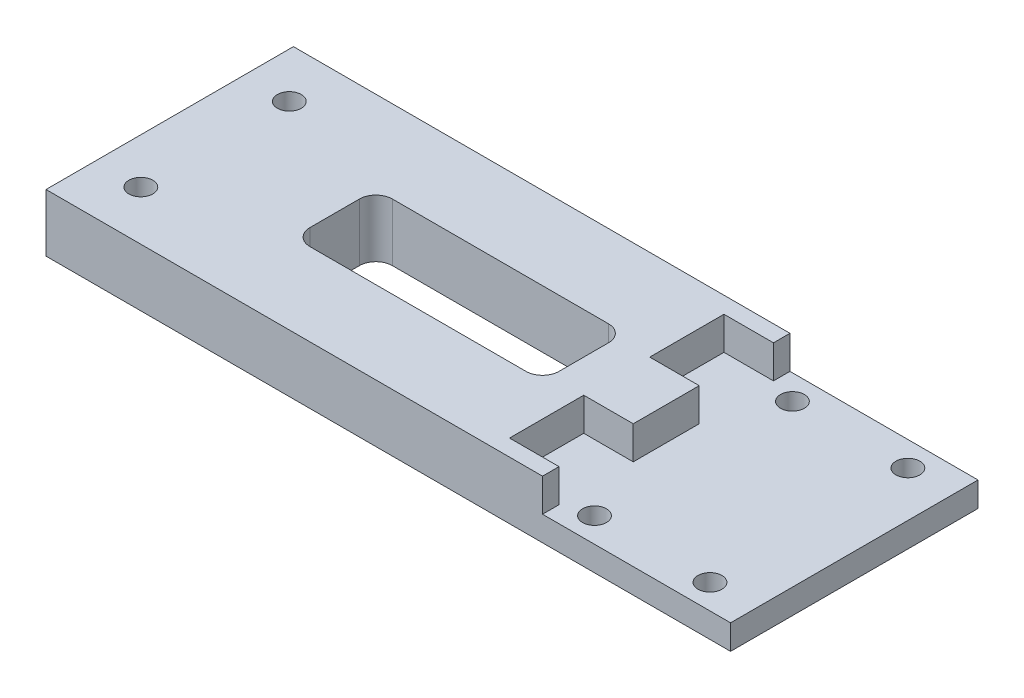
SolidWorks part; units mm, degrees
ref_plane "前视基准面" through (0, 0, 0) normal (0, 0, 1) x (1, 0, 0)
ref_plane "上视基准面" through (0, 0, 0) normal (0, 1, 0) x (1, 0, 0)
ref_plane "右视基准面" through (0, 0, 0) normal (1, 0, 0) x (0, 0, -1)
other "Configuration Table"
sketch "草图1" plane through (0, 0, 0) normal (0, 1, 0) x (1, 0, 0)
  line L1 (0, 0) -> (-88, 0)
  line L2 (0, 0) -> (0, 30)
  line L3 (0, 30) -> (-88, 30)
  line L4 (-88, 0) -> (-88, 30)
  dimension "D1" = 88
  dimension "D2" = 30
extrude "凸台-拉伸1" add sketch "草图1" along normal blind 3
sketch "草图2" plane through (0, 3, 0) normal (0, 1, 0) x (1, 0, 0)
  line L0 (-88, 0) -> (0, 0) construction
  line L1 (0, 30) -> (-27.8, 30)
  line L2 (0, 30) -> (0, 0)
  line L3 (0, 0) -> (-27.8, 0)
  line L4 (-27.8, 30) -> (-27.8, 0)
  dimension "D1" = 27.8
extrude "切除-拉伸1" cut sketch "草图2" against normal blind 1
sketch "草图3" plane through (0, 2, 0) normal (0, 1, 0) x (1, 0, 0)
  line L0 (-27.5, 30) -> (-27.5, 27) construction
  line L3 (-27.5, 27) -> (-24.5, 27) construction
  line L4 (-24.5, 27) -> (-24.5, 3) construction
  line L5 (-24.5, 3) -> (-10.5, 3) construction
  line L6 (-10.5, 3) -> (-10.5, 27) construction
  circle A4 centre (-24.5, 27) radius 1.45
  circle A5 centre (-24.5, 3) radius 1.45
  circle A6 centre (-10.5, 3) radius 1.45
  circle A7 centre (-10.5, 27) radius 1.45
  dimension "D6" = 2.9
  dimension "D1" = 3
  dimension "D2" = 3
  dimension "D3" = 24
  dimension "D4" = 14
  dimension "D5" = 24
extrude "切除-拉伸2" cut sketch "草图3" against normal blind 11
sketch "草图4" plane through (0, 3, 0) normal (0, 1, 0) x (1, 0, 0)
  line L0 (-88, 24) -> (-82.5, 24) construction
  line L2 (-27.8, 30) -> (-88, 30) construction
  line L3 (-88, 15) -> (-85.0043, 15) construction
  line L4 (-88, 30) -> (-88, 0) construction
  circle A0 centre (-82.5, 24) radius 1.45
  circle A1 centre (-82.5, 6) radius 1.45
  dimension "D2" = 2.9
  dimension "D1" = 5.5
  dimension "D3" = 6
extrude "切除-拉伸4" cut sketch "草图4" against normal blind 11
sketch "草图5" plane through (0, 3, 0) normal (0, 1, 0) x (1, 0, 0)
  line L0 (-88, 0) -> (-27.8, 0) construction
  line L1 (-68, 20) -> (-37.8, 20)
  line L2 (-68, 20) -> (-68, 10)
  line L3 (-68, 10) -> (-37.8, 10)
  line L4 (-37.8, 20) -> (-37.8, 10)
  line L5 (-27.8, 30) -> (-88, 30) construction
  line L6 (-27.8, 30) -> (-27.8, 0) construction
  line L7 (-88, 30) -> (-88, 0) construction
  dimension "D1" = 10
  dimension "D2" = 10
  dimension "D3" = 10
  dimension "D4" = 20
extrude "切除-拉伸5" cut sketch "草图5" against normal blind 11
fillet "圆角1" radius 2 4 edges at (-68, 1.5, -10) (-37.8, 1.5, -10) (-37.8, 1.5, -20) (-68, 1.5, -20)
sketch "草图6" plane through (0, 0, 0) normal (0, -1, 0) x (1, 0, 0)
  line L0 (0, -30) -> (-88, -30) construction
  line L1 (0, 0) -> (-5, 0)
  line L2 (0, 0) -> (0, -30)
  line L3 (0, -30) -> (-5, -30)
  line L4 (-5, 0) -> (-5, -30)
  dimension "D1" = 5
extrude "切除-拉伸6" cut sketch "草图6" against normal blind 10
sketch "草图7" plane through (0, 2, 0) normal (0, 1, 0) x (1, 0, 0)
  line L4 (-27.8, 0) -> (-5, 0)
  line L5 (-5, 0) -> (-5, 30)
  line L6 (-5, 30) -> (-27.8, 30)
  line L7 (-27.8, 30) -> (-27.8, 0)
  line L8 (-27.8, 0) -> (-5, 0)
  line L9 (-5, 0) -> (-5, 30)
  line L10 (-5, 30) -> (-27.8, 30)
  line L11 (-27.8, 30) -> (-27.8, 0)
  circle A0 centre (-24.5, 27) radius 1.45 construction
  circle A1 centre (-10.5, 3) radius 1.45 construction
  circle A2 centre (-10.5, 3) radius 1.45
  circle A3 centre (-24.5, 27) radius 1.45
  circle A4 centre (-10.5, 27) radius 1.45 construction
  circle A5 centre (-24.5, 3) radius 1.45 construction
  circle A6 centre (-10.5, 27) radius 1.45
  circle A7 centre (-24.5, 3) radius 1.45
  dimension "D1" = 0
sketch "草图9" plane through (0, 3, 0) normal (0, 1, 0) x (1, 0, 0)
  line L0 (-39.8, 20) -> (-66, 20) construction
  line L1 (-66, 10) -> (-39.8, 10) construction
  line L2 (-68, 18) -> (-68, 12) construction
  line L3 (-37.8, 12) -> (-37.8, 18) construction
  line L4 (-27.8, 0) -> (-27.8, 30)
  line L5 (-27.8, 30) -> (-88, 30)
  line L6 (-88, 30) -> (-88, 0)
  line L7 (-88, 0) -> (-27.8, 0)
  line L8 (-27.8, 0) -> (-27.8, 30)
  line L9 (-27.8, 30) -> (-88, 30)
  line L10 (-88, 30) -> (-88, 0)
  line L11 (-88, 0) -> (-27.8, 0)
  line L12 (-37.8, 12) -> (-37.8, 18)
  line L13 (-68, 18) -> (-68, 12)
  line L14 (-66, 10) -> (-39.8, 10)
  line L15 (-39.8, 20) -> (-66, 20)
  circle A0 centre (-82.5, 24) radius 1.45 construction
  circle A1 centre (-82.5, 6) radius 1.45 construction
  arc A2 (-37.8, 18) -> (-39.8, 20) centre (-39.8, 18) ccw construction
  arc A3 (-66, 20) -> (-68, 18) centre (-66, 18) ccw construction
  arc A4 (-68, 12) -> (-66, 10) centre (-66, 12) ccw construction
  arc A5 (-39.8, 10) -> (-37.8, 12) centre (-39.8, 12) ccw construction
  arc A6 (-39.8, 10) -> (-37.8, 12) centre (-39.8, 12) ccw
  arc A7 (-68, 12) -> (-66, 10) centre (-66, 12) ccw
  arc A8 (-66, 20) -> (-68, 18) centre (-66, 18) ccw
  arc A9 (-37.8, 18) -> (-39.8, 20) centre (-39.8, 18) ccw
  circle A10 centre (-82.5, 6) radius 1.45
  circle A11 centre (-82.5, 24) radius 1.45
  dimension "D1" = 0
extrude "凸台-拉伸4" add sketch "草图9" along normal blind 4
extrude "凸台-拉伸5" add sketch "草图7" along normal blind 1
sketch "草图11" plane through (-27.8, 0, 0) normal (1, 0, 0) x (0, 0, -1)
  line L0 (0, 3) -> (30, 3) construction
  line L6 (30, 3) -> (15, 3)
  line L7 (30, 3) -> (30, 7)
  line L8 (30, 7) -> (15, 7)
  line L9 (15, 3) -> (15, 7)
extrude "切除-拉伸8" cut sketch "草图11" against normal blind 6
sketch "草图12" plane through (-33.8, 0, 0) normal (1, 0, 0) x (0, 0, -1)
  line L0 (15, 3) -> (30, 3) construction
  line L1 (30, 7) -> (28, 7)
  line L2 (30, 7) -> (30, 3)
  line L3 (30, 3) -> (28, 3)
  line L4 (28, 7) -> (28, 3)
  dimension "D1" = 2
extrude "凸台-拉伸6" add sketch "草图12" along normal blind 6
sketch "草图13" plane through (0, 0, -15) normal (0, 0, -1) x (-1, 0, 0)
  line L4 (27.8, 7) -> (27.8, 3)
  line L5 (27.8, 3) -> (33.8, 3)
  line L6 (33.8, 3) -> (33.8, 7)
  line L7 (33.8, 7) -> (27.8, 7)
  line L8 (27.8, 7) -> (27.8, 3)
  line L9 (27.8, 3) -> (33.8, 3)
  line L10 (33.8, 3) -> (33.8, 7)
  line L11 (33.8, 7) -> (27.8, 7)
  dimension "D1" = 0
extrude "凸台-拉伸7" add sketch "草图13" along normal blind 4
sketch "草图14" plane through (0, 0, 0) normal (0, -1, 0) x (1, 0, 0)
  circle A0 centre (-82.5, -6) radius 4
  circle A1 centre (-82.5, -24) radius 4
  dimension "D1" = 8
  dimension "D2" = 8
extrude "切除-拉伸9" cut sketch "草图14" against normal blind 4
sketch "草图15" plane through (-27.8, 0, 0) normal (1, 0, 0) x (0, 0, -1)
  line L0 (0, 7) -> (19, 7) construction
  line L1 (2, 7) -> (11, 7)
  line L2 (2, 7) -> (2, 3)
  line L3 (2, 3) -> (11, 3)
  line L4 (11, 7) -> (11, 3)
  line L5 (19, 3) -> (0, 3) construction
  line L6 (0, 3) -> (0, 7) construction
  dimension "D1" = 9
  dimension "D2" = 2
extrude "切除-拉伸10" cut sketch "草图15" against normal up to surface (6 mm away) up to face at (-33.8, 5, -23.5)
